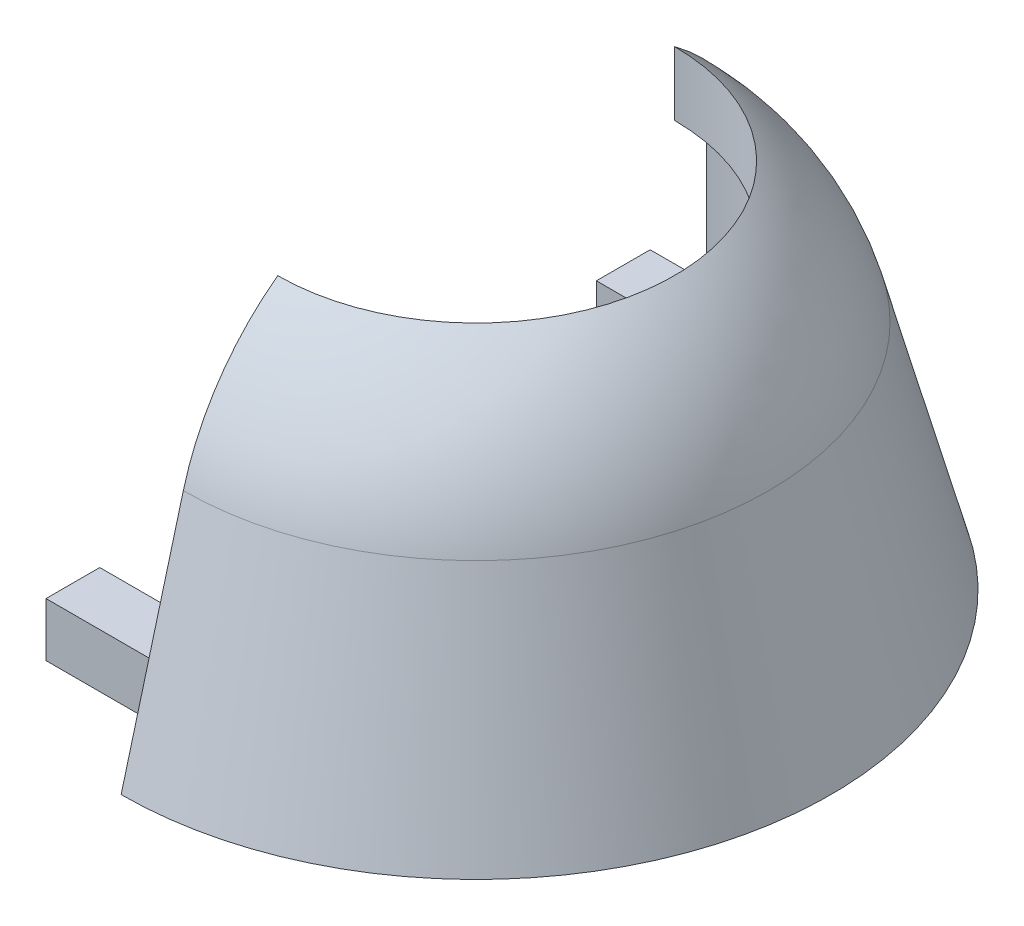
SolidWorks part; units mm, degrees
ref_plane "Front Plane" through (0, 0, 0) normal (0, 0, 1) x (1, 0, 0)
ref_plane "Top Plane" through (0, 0, 0) normal (0, 1, 0) x (1, 0, 0)
ref_plane "Right Plane" through (0, 0, 0) normal (1, 0, 0) x (0, 0, -1)
sketch "Sketch1" plane through (0, 0, 0) normal (0, 1, 0) x (1, 0, 0)
  line L0 (0, 28) -> (0, 18)
  line L1 (0, -18) -> (0, -28)
  arc A0 (0, -18) -> (0, 18) centre (0, 0) ccw
  arc A1 (0, -28) -> (0, 28) centre (0, 0) ccw
extrude "Boss-Extrude1" add sketch "Sketch1" along normal blind 24
sketch "Sketch2" plane through (0, 24, 0) normal (0, 1, 0) x (1, 0, 0)
  line L0 (0, 28) -> (0, 15.5)
  line L1 (0, -28) -> (0, -15.5)
  arc A0 (0, -28) -> (0, 28) centre (0, 0) ccw
  arc A1 (0, -15.5) -> (0, 15.5) centre (0, 0) ccw
extrude "Boss-Extrude2" add sketch "Sketch2" along normal blind 5
chamfer "Chamfer1" distance 30 angle 15 1 edges at (28, 29, 0) first distance on face at (14, 14.5, 0)
sketch "Sketch3" plane through (0, 0, 0) normal (-1, 0, 0) x (0, 0, 1)
  line L0 (-27.7321, 0) -> (-18, 0) construction
  line L1 (18, 0) -> (27.7321, 0) construction
  line L7 (19.4, 6.2) -> (23.6, 6.2)
  line L8 (-23.6, 6.2) -> (-19.4, 6.2)
  line L12 (-18, 24) -> (-18, 0) construction
  line L13 (-23.6, 6.2) -> (-23.6, 2)
  line L14 (-23.6, 2) -> (-19.4, 2)
  line L15 (-19.4, 6.2) -> (-19.4, 2)
  line L16 (-23.6, 6.2) -> (-19.4, 2) construction
  line L17 (-23.6, 2) -> (-19.4, 6.2) construction
  line L18 (19.4, 6.2) -> (19.4, 2)
  line L19 (19.4, 2) -> (23.6, 2)
  line L20 (23.6, 6.2) -> (23.6, 2)
  line L21 (18, 24) -> (18, 0) construction
  point P0 (-21.5, 4.1)
  dimension "D1" = 2
  dimension "D2" = 2
  dimension "D3" = 1.4
  dimension "D4" = 1.4
fillet "Fillet1" radius 20 1 edges at (19.9615, 29, 0)
extrude "Boss-Extrude3" add sketch "Sketch3" along normal blind 10
